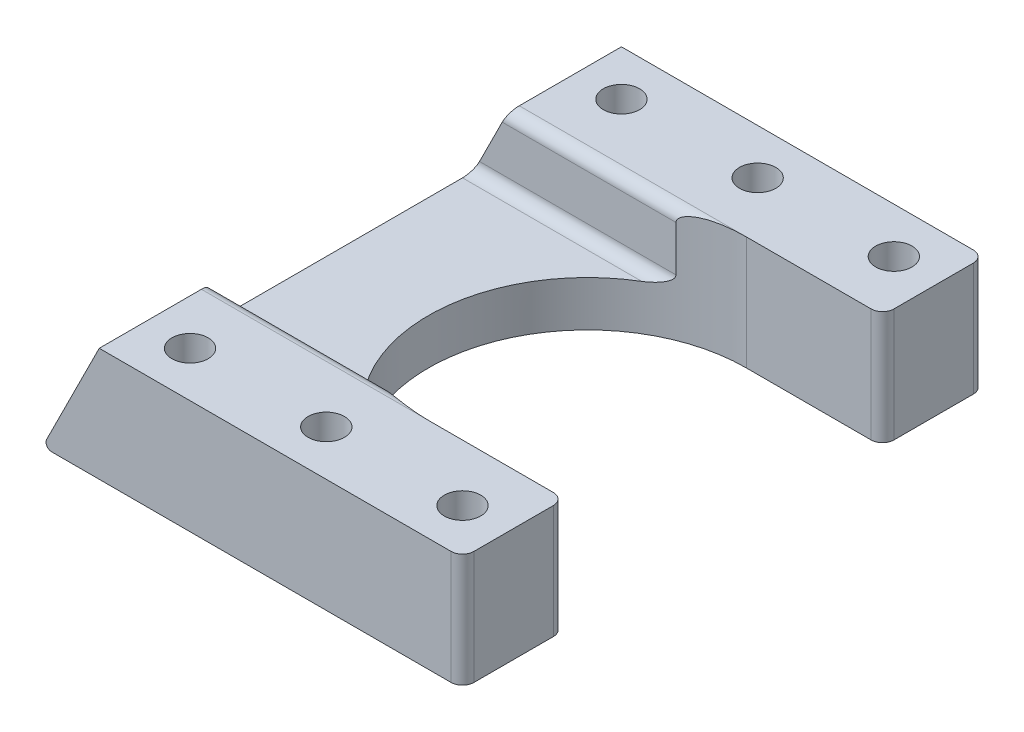
SolidWorks part; units mm, degrees
material "PEI"
ref_plane "Front Plane" through (0, 0, 0) normal (0, 0, 1) x (1, 0, 0)
ref_plane "Top Plane" through (0, 0, 0) normal (0, 1, 0) x (1, 0, 0)
ref_plane "Right Plane" through (0, 0, 0) normal (1, 0, 0) x (0, 0, -1)
sketch "Sketch2" plane through (0, 0, 0) normal (0, 1, 0) x (1, 0, 0)
  line L0 (0, 0) -> (0, 19)
  line L1 (0, 0) -> (-12, 0)
  line L2 (-12, 0) -> (-12, 19)
  line L3 (0, 0) -> (4, 0)
  line L4 (16, -23) -> (-16, -23)
  line L5 (16, -23) -> (16, 23)
  line L6 (16, 23) -> (-16, 23)
  line L7 (-16, -23) -> (-16, 23)
  line L8 (16, -23) -> (-16, 23) construction
  line L9 (16, 23) -> (-16, -23) construction
  line L10 (4, 14) -> (16, 14)
  line L11 (4, -14) -> (16, -14)
  circle A0 centre (-12, 19) radius 1.6
  circle A1 centre (0, 19) radius 1.6
  circle A2 centre (12, 19) radius 1.6
  circle A3 centre (12, -19) radius 1.6
  circle A4 centre (0, -19) radius 1.6
  circle A5 centre (-12, -19) radius 1.6
  circle A6 centre (4, 0) radius 14
  dimension "D3" = 3.2
  dimension "D4" = 3.2
  dimension "D7" = 28
  dimension "D1" = 12
  dimension "D2" = 19
  dimension "D5" = 19
  dimension "D6" = 4
  dimension "D8" = 46
  dimension "D9" = 32
extrude "Boss-Extrude1" add sketch "Sketch2" along normal blind 10 contours A6 L5 L6 L7 L4 A0 A1 A4 A3 A2 A5 region at (-7.6743, 0, -8.7015)
sketch "Sketch4" plane through (0, 0, 23) normal (0, 0, 1) x (1, 0, 0)
  line L0 (-16, 0) -> (-21, 0)
  line L1 (-21, 0) -> (-16, 10)
  line L4 (-16, 0) -> (16, 0)
  line L5 (16, 0) -> (16, 10)
  line L6 (16, 10) -> (-16, 10)
  line L7 (-16, 10) -> (-16, 0)
  line L8 (-16, 0) -> (16, 0)
  line L9 (16, 0) -> (16, 10)
  line L10 (16, 10) -> (-16, 10)
  line L11 (-16, 10) -> (-16, 0)
  line M9 (-16, 10) -> (-16, 0)
  dimension "D2" = 5
  dimension "D1" = 0
extrude "Boss-Extrude2" add sketch "Sketch4" against normal up to surface (46 mm away) contours L1 L0 M9 region at (-17.6667, 3.3333, 23) up to face at (0, 5, -23)
sketch "Sketch5" plane through (0, 10, 0) normal (0, 1, 0) x (1, 0, 0)
  line L0 (0, 0) -> (-21, 0)
  line L1 (0, 13) -> (-21, 13)
  line L2 (0, -13) -> (-21, -13)
  line L4 (-16, -23) -> (-16, 23)
  line L5 (-16, 23) -> (-21, 23)
  line L6 (-21, 23) -> (-21, -23)
  line L7 (-21, -23) -> (-16, -23)
  line L8 (-16, -23) -> (-16, 23)
  line L9 (-16, 23) -> (-21, 23)
  line L10 (-21, 23) -> (-21, -23)
  line L11 (-21, -23) -> (-16, -23)
  line L15 (4, 14) -> (16, 14)
  line L16 (16, 14) -> (16, 23)
  line L17 (16, 23) -> (-16, 23)
  line L18 (-16, 23) -> (-16, -23)
  line L19 (-16, -23) -> (16, -23)
  line L20 (16, -23) -> (16, -14)
  line L21 (16, -14) -> (4, -14)
  line L22 (4, 14) -> (16, 14)
  line L23 (16, 14) -> (16, 23)
  line L24 (16, 23) -> (-16, 23)
  line L25 (-16, 23) -> (-16, -23)
  line L26 (-16, -23) -> (16, -23)
  line L27 (16, -23) -> (16, -14)
  line L28 (16, -14) -> (4, -14)
  arc A1 (4, 14) -> (4, -14) centre (4, 0) ccw
  arc A2 (4, 14) -> (4, -14) centre (4, 0) ccw
  arc M16 (4, -14) -> (4, 14) centre (4, 0) cw
  line M20 (-16, 23) -> (-16, -23)
  dimension "D1" = 0
  dimension "D2" = 0
  dimension "D3" = 13
  dimension "D4" = 13
extrude "Cut-Extrude1" cut sketch "Sketch5" against normal blind 6 contours L1 L0 M16 M20 | L1 L10 L0 M20 | L2 L0 M16 M20 | L0 L10 L2 M20 region at (-11.4463, 10, 7.5042) region at (-11.4463, 10, -7.5042) region at (-18.5, 10, 6.5) region at (-18.5, 10, -6.5)
fillet "Fillet1" radius 1 4 edges at (-10.0981, 4, 13) (-10.0981, 4, -13) (-8.5981, 10, 13) (-8.5981, 10, -13)
fillet "Fillet2" radius 0.5 1 edges at (-21, 0, 0)
fillet "Fillet3" radius 1 4 edges at (16, 5, -23) (16, 5, -14) (16, 5, 14) (16, 5, 23)
